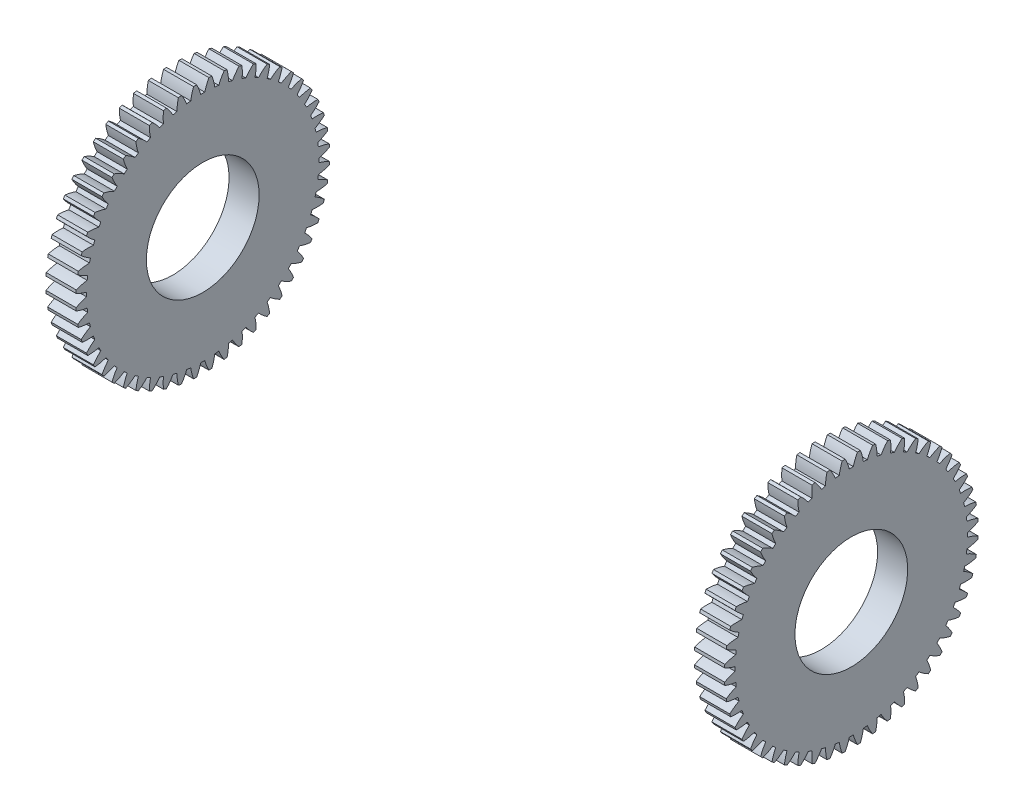
SolidWorks part; units mm, degrees
material "CF Nylon"
ref_plane "Plane1" through (0, 0, 0) normal (0, 0, 1) x (1, 0, 0)
ref_plane "Plane2" through (0, 0, 0) normal (0, 1, 0) x (1, 0, 0)
ref_plane "Plane3" through (0, 0, 0) normal (1, 0, 0) x (0, 0, -1)
other "Configuration Table"
ref_plane "Plane5" through (52.25, 0, 0) normal (1, 0, 0) x (0, 0, -1)
sketch "HoldingSke" plane through (0, 0, 0) normal (0, 1, 0) x (1, 0, 0)
  line L0 (0, 0) -> (500.4096, -640.4951)
  line L1 (-15, 0) -> (100, 0) construction
  line L2 (0, 0) -> (-2.1039, 2.3779)
  line L3 (0, 0) -> (-11.863, 4.5341)
  line L4 (0, 0) -> (5.3169, 6.8053)
  line L5 (0, 0) -> (-47.5972, -17.7524)
  line L6 (0, 0) -> (-4.2111, -2.8413)
  line L7 (-2.1039, 2.3779) -> (8.8308, 51.9871)
  line L8 (-76.2, 54.61) -> (-75.184, 54.61)
  line L9 (-71.009, 38.7566) -> (-53.1078, 45.2721)
  line L10 (-76.2, 71.12) -> (104.1128, 71.12)
  line L11 (0, 0) -> (-5.08, 0)
  line L12 (-76.2, 101.6) -> (-76.1716, 101.6)
  line L13 (24.9733, 27.94) -> (52.9518, 28.4284)
  line L14 (24.9733, 27.94) -> (25.0241, 27.9398)
  line L15 (24.9733, 27.94) -> (100.4021, 29.52)
  circle A0 centre (0, 0) radius 0.3969
  circle A1 centre (0, 0) radius 19.6342
  circle A2 centre (0, 0) radius 38.1
  circle A3 centre (0, 0) radius 0.3969
  dimension "MHD" = 39.2684
  dimension "Hub_dia" = 76.2
  dimension "Bore" = 0.7937
  dimension "MBD" = 0.7937
  dimension "Num_teeth" = 52
  dimension "Pitch" = 812.8
  dimension "Overall_len" = 50.8
  dimension "Show_teeth" = 52
  dimension "Thickness" = 5.08
  dimension "OAL" = 50.8001
  dimension "T_dim" = 1.016
  dimension "Ap" = 20
  dimension "H" = 19.05
  dimension "Pitch_radius" = 180.3128
  dimension "Width" = 5.08
  dimension "Backlash" = 0.0284
  dimension "Addendum_fac" = 1
  dimension "Dedendum_fac" = 1.2
  dimension "Clearance_fac" = 0.2
  dimension "Dedendum_add" = 0.0508
sketch "BasProSke" plane through (0, 0, 0) normal (0, 1, 0) x (1, 0, 0)
  line L0 (-10, 0) -> (60, 0) construction
  line L1 (52.25, 0) -> (52.25, 21.4312)
  line L2 (52.25, 0) -> (57.33, 0)
  line L3 (57.33, 0) -> (57.33, 21.4312)
  line L4 (57.33, 21.4312) -> (52.25, 21.4312)
  line L5 (52.25, -16.025) -> (52.25, 16.025) construction
  point P3 (52.25, 0)
  dimension "Thickness" = 5.08
  dimension "Diameter" = 42.8625
revolve "Base-Revolve" add sketch "BasProSke" angle 360 about L0
sketch "TooCutSke" plane through (0, 0, 0) normal (1, 0, 0) x (0, 0, -1)
  line L1 (0, 0) -> (0, 107) construction
  line L2 (0, 0) -> (-0.6731, 20.6265) construction
  line L3 (0, 0) -> (-2.4912, 41.1838) construction
  line L4 (-0.6731, 20.6265) -> (-1.2456, 20.5919) construction
  arc A0 (0.3404, 19.6312) -> (-0.3404, 19.6312) centre (0, 0) ccw
  arc A1 (1.0518, 21.4309) -> (-1.0518, 21.4309) centre (0, 0) ccw
  circle A2 centre (0, 0) radius 20.6375 construction
  circle A3 centre (0, 0) radius 19.3929 construction
  arc A4 (-0.3404, 19.6312) -> (-1.0518, 21.4309) centre (-8.3202, 17.5174) ccw
  arc A5 (1.0518, 21.4309) -> (0.3404, 19.6312) centre (8.3202, 17.5174) ccw
  dimension "Root_dia" = 39.2684
  dimension "Overcut_dia" = 42.9133
  dimension "Pitch_dia" = 41.275
  dimension "Base_dia" = 38.7858
  dimension "Flank_rad" = 8.255
  dimension "Half_ang" = 3.462
  dimension "Half_CT" = 0.5735
extrude "ToothCut" cut sketch "TooCutSke" along normal through all
fillet "Breaks" [suppressed] radius 0.0159 tangent propagation no
fillet "RootFillets" [suppressed] radius 0.2095
pattern_circular "TeethCuts" count 52 every 6.923 about axis through (-10, 0, 0) along (1, 0, 0) of "ToothCut", "RootFillets", "Breaks"
sketch "HubNeaOneSke" plane through (52.25, 0, 0) normal (-1, 0, 0) x (0, 0, 1)
  circle A0 centre (0, 0) radius 19.6342
  dimension "Diameter" = 39.2684
extrude "HubNearOne" [suppressed] add sketch "HubNeaOneSke" along normal blind 45.7201
sketch "HubNeaBotSke" plane through (52.25, 0, 0) normal (-1, 0, 0) x (0, 0, 1)
  circle A0 centre (0, 0) radius 19.6342
  dimension "Diameter" = 39.2684
extrude "HubNearBoth" [suppressed] add sketch "HubNeaBotSke" along normal blind 22.86
ref_plane "FarPln" through (5.08, 0, 0) normal (1, 0, 0) x (0, 0, -1)
sketch "HubFarSke" plane through (5.08, 0, 0) normal (1, 0, 0) x (0, 0, -1)
  circle A0 centre (0, 0) radius 19.6342
  dimension "Diameter" = 39.2684
extrude "HubFar" [suppressed] add sketch "HubFarSke" along normal blind 22.86
sketch "BorSke" plane through (52.25, 0, 0) normal (1, 0, 0) x (0, 0, -1)
  circle A0 centre (0, 0) radius 9.525 construction
  circle A2 centre (0, 0) radius 9.525
extrude "Bore" cut sketch "BorSke" along normal mid plane 101.6001
sketch "KeySke" plane through (0, 0, 0) normal (1, 0, 0) x (0, 0, -1)
  line L0 (-0.127, 0) -> (-0.127, 0.6191)
  line L1 (-0.127, 0.6191) -> (0.127, 0.6191)
  line L2 (0.127, 0.6191) -> (0.127, 0)
  line L3 (0, 0) -> (0, 34) construction
  line L4 (-0.127, 0) -> (0.127, 0)
  dimension "Offset" = 0.6191
  dimension "Width" = 0.254
extrude "Keyway" [suppressed] cut sketch "KeySke" along normal mid plane 101.6001
pattern_circular "Keyway2" [suppressed] count 2 every 90 about axis through (-10, 0, 0) along (1, 0, 0) reverse direction yes
ref_plane "Plane4" through (-52.25, 0, 0) normal (1, 0, 0) x (0, 0, -1)
mirror "Mirror1" about plane through (0, 0, 0) normal (1, 0, 0) of bodies 103 104
equation "' \"Pitch@HoldingSke\" = 4"
equation "' \"Num_teeth@HoldingSke\" = 12"
equation "' \"Ap@HoldingSke\" =  20"
equation "' \"Ap@HoldingSke\" = 20"
equation "' \"Width@HoldingSke\" = 0.5"
equation "' \"Hub_dia@HoldingSke\"= 1"
equation "' \"Hub_dia@HoldingSke\" = 1"
equation "' \"Overall_len@HoldingSke\" = 1.0"
equation "' \"Bore@HoldingSke\" = 0.75"
equation "' \"T_dim@HoldingSke\" = 0.85"
equation "' \"Width@KeySke\" = 0.25"
equation "' \"Show_teeth@HoldingSke\" = 13"
equation "' \"Backlash@HoldingSke\" = 0.009"
equation "' \"Addendum_fac@HoldingSke\" = 1.0"
equation "' \"Dedendum_fac@HoldingSke\" = 1.25"
equation "' \"Dedendum_add@HoldingSke\" = 0.00005"
equation "' \"Clearance_fac@HoldingSke\" = 0.25"
equation "' \"Pitch@HoldingSke\" = 0.5"
equation "' \"Num_teeth@HoldingSke\" = 23"
equation "' \"Show_teeth@HoldingSke\" = 23"
equation "' \"Backlash@HoldingSke\" = 0.0375"
equation "\"Overcut_dia@TooCutSke\" = (\"Num_teeth@HoldingSke\" + 2 * \"Addendum_fac@HoldingSke\") / \"Pitch@HoldingSke\" + 0.002"
equation "\"Pitch_dia@TooCutSke\" = \"Num_teeth@HoldingSke\" / \"Pitch@HoldingSke\""
equation "\"Base_dia@TooCutSke\" = \"Num_teeth@HoldingSke\" / \"Pitch@HoldingSke\" * cos((\"Ap@HoldingSke\"  * 3.14159265 / 180))"
equation "\"Root_dia@TooCutSke\" = (\"Num_teeth@HoldingSke\" + 2) / \"Pitch@HoldingSke\" - 2 * (\"Addendum_fac@HoldingSke\" + \"Dedendum_fac@HoldingSke\") / \"Pitch@HoldingSke\" - \"Dedendum_add@HoldingSke\" * 2"
equation "\"Half_ang@TooCutSke\" = 180 / \"Num_teeth@HoldingSke\""
equation "\"Half_CT@TooCutSke\" = \"Num_teeth@HoldingSke\" / \"Pitch@HoldingSke\" * sin((3.14159265 / 2 / \"Num_teeth@HoldingSke\")) / 2 - 7 * \"Backlash@HoldingSke\" / 4"
equation "\"Flank_rad@TooCutSke\" = \"Num_teeth@HoldingSke\" / \"Pitch@HoldingSke\" / 5"
equation "\"Radius@RootFillets\" = \"Clearance_fac@HoldingSke\" / \"Pitch@HoldingSke\" + \"Dedendum_add@HoldingSke\""
equation "\"Break_rad@Breaks\" = 0.02 / \"Pitch@HoldingSke\""
equation "\"Thickness@HoldingSke\" = \"Width@HoldingSke\""
equation "\"OAL@HoldingSke\" = \"Thickness@HoldingSke\""
equation "\"MHD@HoldingSke\" = (\"Num_teeth@HoldingSke\" + 2) / \"Pitch@HoldingSke\" - 2 * (\"Addendum_fac@HoldingSke\" + \"Dedendum_fac@HoldingSke\")  / \"Pitch@HoldingSke\" - \"Dedendum_add@HoldingSke\" * 2"
equation "\"MBD@HoldingSke\" = (\"Num_teeth@HoldingSke\" + 2) / \"Pitch@HoldingSke\" - 2 * (\"Addendum_fac@HoldingSke\" + \"Dedendum_fac@HoldingSke\")  / \"Pitch@HoldingSke\" - \"Dedendum_add@HoldingSke\" * 2 - 0.002"
equation "\"MHD@HoldingSke\" = ((sgn( \"MHD@HoldingSke\" - \"Hub_dia@HoldingSke\" )-1)*( \"MHD@HoldingSke\" - \"Hub_dia@HoldingSke\" ))/-2+ \"Hub_dia@HoldingSke\""
equation "\"MBD@HoldingSke\" = ((sgn( \"MBD@HoldingSke\" - \"Bore@HoldingSke\" )-1)*( \"MBD@HoldingSke\" - \"Bore@HoldingSke\" ))/-2+ \"Bore@HoldingSke\""
equation "\"OAL@HoldingSke\" = ((sgn( \"OAL@HoldingSke\" - \"Overall_len@HoldingSke\" )+1)*( \"OAL@HoldingSke\" - \"Overall_len@HoldingSke\" ))/2 + \"Overall_len@HoldingSke\" + 0.000002"
equation "\"Num_teeth@TeethCuts\" = int( \"Show_teeth@HoldingSke\" ) + 1"
equation "\"Num_teeth@TeethCuts\" = ((sgn( \"Num_teeth@TeethCuts\" - \"Num_teeth@HoldingSke\" )-1)*( \"Num_teeth@TeethCuts\" - \"Num_teeth@HoldingSke\" ))/-2+ \"Num_teeth@HoldingSke\""
equation "\"Num_teeth@TeethCuts\" = ((sgn( \"Num_teeth@TeethCuts\" - 2.0)+1)*( \"Num_teeth@TeethCuts\" - 2.0))/2 +2.0"
equation "\"Angle@TeethCuts\" = 360.0 / \"Num_teeth@HoldingSke\""
equation "\"Diameter@BasProSke\" = (\"Num_teeth@HoldingSke\" + 2 * \"Addendum_fac@HoldingSke\") / \"Pitch@HoldingSke\""
equation "\"Thickness@BasProSke\"  = \"Thickness@HoldingSke\""
equation "' \"Fillet_rad@BasProSke\" =  \"Thickness@HoldingSke\" * 0.05"
equation "' \"Fillet_rad@BasProSke\" = \"Thickness@HoldingSke\" * 0.05"
equation "\"MHD@HoldingSke\" = ((sgn( \"MHD@HoldingSke\" - \"Root_dia@TooCutSke\" )-1)*( \"MHD@HoldingSke\" - \"Root_dia@TooCutSke\" ))/-2+ \"Root_dia@TooCutSke\""
equation "\"Diameter@HubNeaOneSke\" = \"MHD@HoldingSke\""
equation "\"Length@HubNearOne\" = \"OAL@HoldingSke\" - \"Thickness@BasProSke\""
equation "\"Diameter@HubNeaBotSke\" = \"MHD@HoldingSke\""
equation "\"Length@HubNearBoth\" = ( \"OAL@HoldingSke\" - \"Thickness@BasProSke\" ) / 2.0"
equation "\"Thickness@FarPln\" = \"Thickness@BasProSke\""
equation "\"Diameter@HubFarSke\" = \"MHD@HoldingSke\""
equation "\"Length@HubFar\" = ( \"OAL@HoldingSke\" - \"Thickness@BasProSke\" ) / 2.0"
equation "\"D1@Bore\" = \"OAL@HoldingSke\" * 2.0"
equation "\"D1@Keyway\" = \"OAL@HoldingSke\" * 2.0"
equation "\"Offset@KeySke\" = \"T_dim@HoldingSke\" - \"MBD@HoldingSke\" / 2.0"
